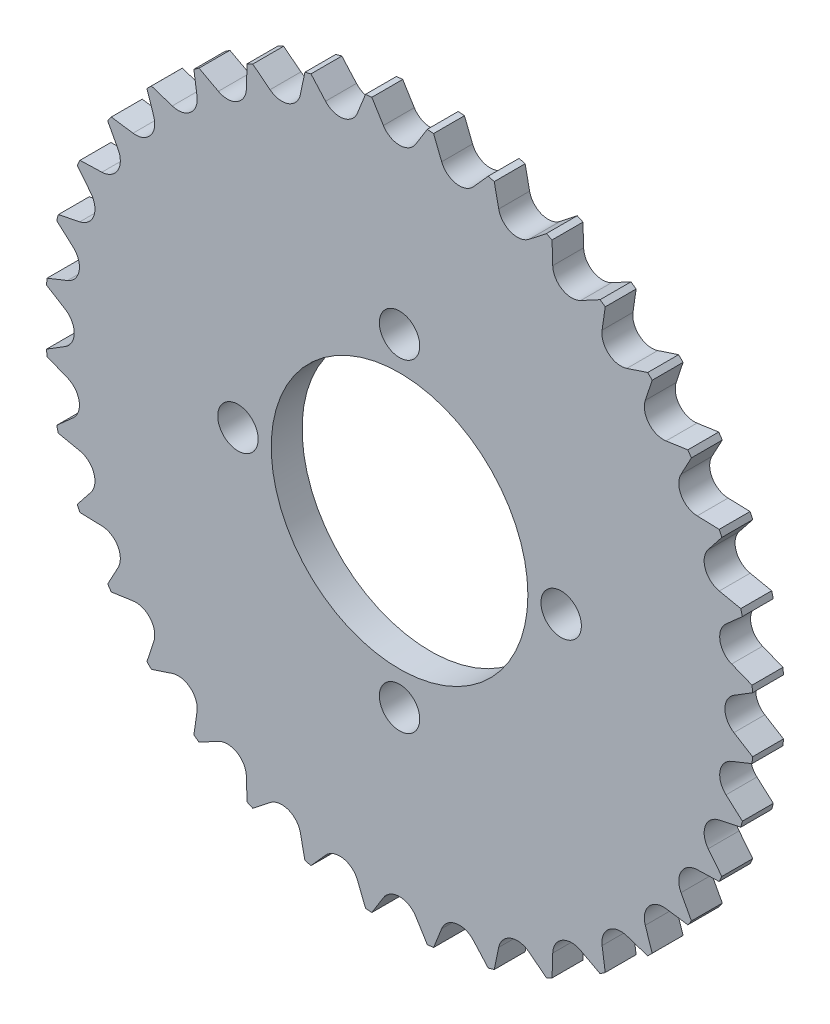
SolidWorks part; units mm, degrees
material "Plain Carbon Steel"
ref_plane "Front Plane" through (0, 0, 0) normal (0, 0, 1) x (1, 0, 0)
ref_plane "Top Plane" through (0, 0, 0) normal (0, 1, 0) x (1, 0, 0)
ref_plane "Right Plane" through (0, 0, 0) normal (1, 0, 0) x (0, 0, -1)
sketch "Sketch1" plane through (0, 0, 0) normal (0, 0, 1) x (1, 0, 0)
  line L0 (3.4006, 70.3439) -> (6.0855, 74.679)
  line L1 (3.4006, 70.3439) -> (8.8661, 69.8657) construction
  line L2 (6.9749, 74.6012) -> (8.8661, 69.8657)
  line L3 (3.4006, 70.3439) -> (0, 0) construction
  line L4 (0, 0) -> (8.8661, 69.8657) construction
  line L5 (15.5641, 68.6847) -> (18.9609, 72.4877)
  line L6 (19.8233, 72.2567) -> (20.8635, 67.2647)
  line L7 (27.2546, 64.9386) -> (31.2602, 68.094)
  line L8 (32.0693, 67.7166) -> (32.2269, 62.6199)
  line L9 (38.117, 59.2193) -> (42.6097, 61.6312)
  line L10 (43.341, 61.1191) -> (42.6111, 56.0725)
  line L11 (47.8212, 51.7007) -> (52.6645, 53.2958)
  line L12 (53.2958, 52.6645) -> (51.7007, 47.8212)
  line L13 (56.0725, 42.6111) -> (61.1191, 43.341)
  line L14 (61.6312, 42.6097) -> (59.2193, 38.117)
  line L15 (62.6199, 32.2269) -> (67.7166, 32.0693)
  line L16 (68.094, 31.2602) -> (64.9386, 27.2546)
  line L17 (67.2647, 20.8635) -> (72.2567, 19.8233)
  line L18 (72.4877, 18.9609) -> (68.6847, 15.5641)
  line L19 (69.8657, 8.8661) -> (74.6012, 6.9749)
  line L20 (74.679, 6.0855) -> (70.3439, 3.4006)
  line L21 (70.3439, -3.4006) -> (74.679, -6.0855)
  line L22 (74.6012, -6.9749) -> (69.8657, -8.8661)
  line L23 (68.6847, -15.5641) -> (72.4877, -18.9609)
  line L24 (72.2567, -19.8233) -> (67.2647, -20.8635)
  line L25 (64.9386, -27.2546) -> (68.094, -31.2602)
  line L26 (67.7166, -32.0693) -> (62.6199, -32.2269)
  line L27 (59.2193, -38.117) -> (61.6312, -42.6097)
  line L28 (61.1191, -43.341) -> (56.0725, -42.6111)
  line L29 (51.7007, -47.8212) -> (53.2958, -52.6645)
  line L30 (52.6645, -53.2958) -> (47.8212, -51.7007)
  line L31 (42.6111, -56.0725) -> (43.341, -61.1191)
  line L32 (42.6097, -61.6312) -> (38.117, -59.2193)
  line L33 (32.2269, -62.6199) -> (32.0693, -67.7166)
  line L34 (31.2602, -68.094) -> (27.2546, -64.9386)
  line L35 (20.8635, -67.2647) -> (19.8233, -72.2567)
  line L36 (18.9609, -72.4877) -> (15.5641, -68.6847)
  line L37 (8.8661, -69.8657) -> (6.9749, -74.6012)
  line L38 (6.0855, -74.679) -> (3.4006, -70.3439)
  line L39 (-3.4006, -70.3439) -> (-6.0855, -74.679)
  line L40 (-6.9749, -74.6012) -> (-8.8661, -69.8657)
  line L41 (-15.5641, -68.6847) -> (-18.9609, -72.4877)
  line L42 (-19.8233, -72.2567) -> (-20.8635, -67.2647)
  line L43 (-27.2546, -64.9386) -> (-31.2602, -68.094)
  line L44 (-32.0693, -67.7166) -> (-32.2269, -62.6199)
  line L45 (-38.117, -59.2193) -> (-42.6097, -61.6312)
  line L46 (-43.341, -61.1191) -> (-42.6111, -56.0725)
  line L47 (-47.8212, -51.7007) -> (-52.6645, -53.2958)
  line L48 (-53.2958, -52.6645) -> (-51.7007, -47.8212)
  line L49 (-56.0725, -42.6111) -> (-61.1191, -43.341)
  line L50 (-61.6312, -42.6097) -> (-59.2193, -38.117)
  line L51 (-62.6199, -32.2269) -> (-67.7166, -32.0693)
  line L52 (-68.094, -31.2602) -> (-64.9386, -27.2546)
  line L53 (-67.2647, -20.8635) -> (-72.2567, -19.8233)
  line L54 (-72.4877, -18.9609) -> (-68.6847, -15.5641)
  line L55 (-69.8657, -8.8661) -> (-74.6012, -6.9749)
  line L56 (-74.679, -6.0855) -> (-70.3439, -3.4006)
  line L57 (-70.3439, 3.4006) -> (-74.679, 6.0855)
  line L58 (-74.6012, 6.9749) -> (-69.8657, 8.8661)
  line L59 (-68.6847, 15.5641) -> (-72.4877, 18.9609)
  line L60 (-72.2567, 19.8233) -> (-67.2647, 20.8635)
  line L61 (-64.9386, 27.2546) -> (-68.094, 31.2602)
  line L62 (-67.7166, 32.0693) -> (-62.6199, 32.2269)
  line L63 (-59.2193, 38.117) -> (-61.6312, 42.6097)
  line L64 (-61.1191, 43.341) -> (-56.0725, 42.6111)
  line L65 (-51.7007, 47.8212) -> (-53.2958, 52.6645)
  line L66 (-52.6645, 53.2958) -> (-47.8212, 51.7007)
  line L67 (-42.6111, 56.0725) -> (-43.341, 61.1191)
  line L68 (-42.6097, 61.6312) -> (-38.117, 59.2193)
  line L69 (-32.2269, 62.6199) -> (-32.0693, 67.7166)
  line L70 (-31.2602, 68.094) -> (-27.2546, 64.9386)
  line L71 (-20.8635, 67.2647) -> (-19.8233, 72.2567)
  line L72 (-18.9609, 72.4877) -> (-15.5641, 68.6847)
  line L73 (-8.8661, 69.8657) -> (-6.9749, 74.6012)
  line L74 (-6.0855, 74.679) -> (-3.4006, 70.3439)
  line L83 (0, 72.45) -> (0, 0) construction
  line L84 (0, 0) -> (6.5105, 74.4157) construction
  circle A0 centre (0, 0) radius 72.45 construction
  arc A1 (-3.9985, 72.3396) -> (3.4006, 70.3439) centre (0, 72.45) ccw
  arc A2 (4.6139, 72.3029) -> (8.0115, 72.0057) centre (0, 0) cw
  arc A3 (6.0855, 74.679) -> (6.9749, 74.6012) centre (6.5105, 74.4157) cw
  arc A4 (8.6239, 71.9349) -> (15.5641, 68.6847) centre (12.5808, 71.3493) ccw
  arc A5 (18.9609, 72.4877) -> (19.8233, 72.2567) centre (19.3338, 72.1547) cw
  arc A6 (20.9843, 69.3445) -> (27.2546, 64.9386) centre (24.7794, 68.0807) ccw
  arc A7 (31.2602, 68.094) -> (32.0693, 67.7166) centre (31.5696, 67.7012) cw
  arc A8 (32.707, 64.6472) -> (38.117, 59.2193) centre (36.225, 62.7435) ccw
  arc A9 (42.6097, 61.6312) -> (43.341, 61.1191) centre (42.8462, 61.1907) cw
  arc A10 (43.436, 57.9855) -> (47.8212, 51.7007) centre (46.57, 55.4999) ccw
  arc A11 (52.6645, 53.2958) -> (53.2958, 52.6645) centre (52.8209, 52.8209) cw
  arc A12 (52.8452, 49.562) -> (56.0725, 42.6111) centre (55.4999, 46.57) ccw
  arc A13 (61.1191, 43.341) -> (61.6312, 42.6097) centre (61.1907, 42.8462) cw
  arc A14 (60.6487, 39.6326) -> (62.6199, 32.2269) centre (62.7435, 36.225) ccw
  arc A15 (67.7166, 32.0693) -> (68.094, 31.2602) centre (67.7012, 31.5696) cw
  arc A16 (66.6094, 28.4989) -> (67.2647, 20.8635) centre (68.0807, 24.7794) ccw
  arc A17 (72.2567, 19.8233) -> (72.4877, 18.9609) centre (72.1547, 19.3338) cw
  arc A18 (70.5463, 16.4994) -> (69.8657, 8.8661) centre (71.3493, 12.5808) ccw
  arc A19 (74.6012, 6.9749) -> (74.679, 6.0855) centre (74.4157, 6.5105) cw
  arc A20 (72.3396, 3.9985) -> (70.3439, -3.4006) centre (72.45, 0) ccw
  arc A21 (74.679, -6.0855) -> (74.6012, -6.9749) centre (74.4157, -6.5105) cw
  arc A22 (71.9349, -8.6239) -> (68.6847, -15.5641) centre (71.3493, -12.5808) ccw
  arc A23 (72.4877, -18.9609) -> (72.2567, -19.8233) centre (72.1547, -19.3338) cw
  arc A24 (69.3445, -20.9843) -> (64.9386, -27.2546) centre (68.0807, -24.7794) ccw
  arc A25 (68.094, -31.2602) -> (67.7166, -32.0693) centre (67.7012, -31.5696) cw
  arc A26 (64.6472, -32.707) -> (59.2193, -38.117) centre (62.7435, -36.225) ccw
  arc A27 (61.6312, -42.6097) -> (61.1191, -43.341) centre (61.1907, -42.8462) cw
  arc A28 (57.9855, -43.436) -> (51.7007, -47.8212) centre (55.4999, -46.57) ccw
  arc A29 (53.2958, -52.6645) -> (52.6645, -53.2958) centre (52.8209, -52.8209) cw
  arc A30 (49.562, -52.8452) -> (42.6111, -56.0725) centre (46.57, -55.4999) ccw
  arc A31 (43.341, -61.1191) -> (42.6097, -61.6312) centre (42.8462, -61.1907) cw
  arc A32 (39.6326, -60.6487) -> (32.2269, -62.6199) centre (36.225, -62.7435) ccw
  arc A33 (32.0693, -67.7166) -> (31.2602, -68.094) centre (31.5696, -67.7012) cw
  arc A34 (28.4989, -66.6094) -> (20.8635, -67.2647) centre (24.7794, -68.0807) ccw
  arc A35 (19.8233, -72.2567) -> (18.9609, -72.4877) centre (19.3338, -72.1547) cw
  arc A36 (16.4994, -70.5463) -> (8.8661, -69.8657) centre (12.5808, -71.3493) ccw
  arc A37 (6.9749, -74.6012) -> (6.0855, -74.679) centre (6.5105, -74.4157) cw
  arc A38 (3.9985, -72.3396) -> (-3.4006, -70.3439) centre (0, -72.45) ccw
  arc A39 (-6.0855, -74.679) -> (-6.9749, -74.6012) centre (-6.5105, -74.4157) cw
  arc A40 (-8.6239, -71.9349) -> (-15.5641, -68.6847) centre (-12.5808, -71.3493) ccw
  arc A41 (-18.9609, -72.4877) -> (-19.8233, -72.2567) centre (-19.3338, -72.1547) cw
  arc A42 (-20.9843, -69.3445) -> (-27.2546, -64.9386) centre (-24.7794, -68.0807) ccw
  arc A43 (-31.2602, -68.094) -> (-32.0693, -67.7166) centre (-31.5696, -67.7012) cw
  arc A44 (-32.707, -64.6472) -> (-38.117, -59.2193) centre (-36.225, -62.7435) ccw
  arc A45 (-42.6097, -61.6312) -> (-43.341, -61.1191) centre (-42.8462, -61.1907) cw
  arc A46 (-43.436, -57.9855) -> (-47.8212, -51.7007) centre (-46.57, -55.4999) ccw
  arc A47 (-52.6645, -53.2958) -> (-53.2958, -52.6645) centre (-52.8209, -52.8209) cw
  arc A48 (-52.8452, -49.562) -> (-56.0725, -42.6111) centre (-55.4999, -46.57) ccw
  arc A49 (-61.1191, -43.341) -> (-61.6312, -42.6097) centre (-61.1907, -42.8462) cw
  arc A50 (-60.6487, -39.6326) -> (-62.6199, -32.2269) centre (-62.7435, -36.225) ccw
  arc A51 (-67.7166, -32.0693) -> (-68.094, -31.2602) centre (-67.7012, -31.5696) cw
  arc A52 (-66.6094, -28.4989) -> (-67.2647, -20.8635) centre (-68.0807, -24.7794) ccw
  arc A53 (-72.2567, -19.8233) -> (-72.4877, -18.9609) centre (-72.1547, -19.3338) cw
  arc A54 (-70.5463, -16.4994) -> (-69.8657, -8.8661) centre (-71.3493, -12.5808) ccw
  arc A55 (-74.6012, -6.9749) -> (-74.679, -6.0855) centre (-74.4157, -6.5105) cw
  arc A56 (-72.3396, -3.9985) -> (-70.3439, 3.4006) centre (-72.45, 0) ccw
  arc A57 (-74.679, 6.0855) -> (-74.6012, 6.9749) centre (-74.4157, 6.5105) cw
  arc A58 (-71.9349, 8.6239) -> (-68.6847, 15.5641) centre (-71.3493, 12.5808) ccw
  arc A59 (-72.4877, 18.9609) -> (-72.2567, 19.8233) centre (-72.1547, 19.3338) cw
  arc A60 (-69.3445, 20.9843) -> (-64.9386, 27.2546) centre (-68.0807, 24.7794) ccw
  arc A61 (-68.094, 31.2602) -> (-67.7166, 32.0693) centre (-67.7012, 31.5696) cw
  arc A62 (-64.6472, 32.707) -> (-59.2193, 38.117) centre (-62.7435, 36.225) ccw
  arc A63 (-61.6312, 42.6097) -> (-61.1191, 43.341) centre (-61.1907, 42.8462) cw
  arc A64 (-57.9855, 43.436) -> (-51.7007, 47.8212) centre (-55.4999, 46.57) ccw
  arc A65 (-53.2958, 52.6645) -> (-52.6645, 53.2958) centre (-52.8209, 52.8209) cw
  arc A66 (-49.562, 52.8452) -> (-42.6111, 56.0725) centre (-46.57, 55.4999) ccw
  arc A67 (-43.341, 61.1191) -> (-42.6097, 61.6312) centre (-42.8462, 61.1907) cw
  arc A68 (-39.6326, 60.6487) -> (-32.2269, 62.6199) centre (-36.225, 62.7435) ccw
  arc A69 (-32.0693, 67.7166) -> (-31.2602, 68.094) centre (-31.5696, 67.7012) cw
  arc A70 (-28.4989, 66.6094) -> (-20.8635, 67.2647) centre (-24.7794, 68.0807) ccw
  arc A71 (-19.8233, 72.2567) -> (-18.9609, 72.4877) centre (-19.3338, 72.1547) cw
  arc A72 (-16.4994, 70.5463) -> (-8.8661, 69.8657) centre (-12.5808, 71.3493) ccw
  arc A73 (-6.9749, 74.6012) -> (-6.0855, 74.679) centre (-6.5105, 74.4157) cw
  point P289 (0, 0)
  dimension "D1" = 144.9
  dimension "D2" = 4
  dimension "D5" = 0.5
  dimension "D6" = 74.7
  dimension "D3" = 5
  dimension "D4" = 36
extrude "Boss-Extrude1" add sketch "Sketch1" along normal blind 6.5 contours L74 A73 L73 A72 L72 A71 L71 A70 L70 A69 L69 A68 L68 A67 L67 A66 L66 A65 L65 A64 L64 A63 L63 A62 L62 A61 L61 A60 L60 A59 L59 A58 L58 A57 L57 A56 | A3 L0 A2 L2 region at (-0.0022, -0.0255, 0) region at (6.4054, 73.214, 0)
sketch "Sketch5" plane through (0, 0, 0) normal (0, 0, -1) x (-1, 0, 0)
  line L0 (0, 68.45) -> (2.9886, 68.1885)
  line L1 (0, 68.45) -> (0.611, 75.4338)
  line L2 (11.8862, 67.4101) -> (12.4972, 74.3939)
  line L3 (0.611, 75.4338) -> (12.4972, 74.3939)
  line L4 (8.8976, 67.6716) -> (11.8862, 67.4101)
  arc A0 (2.9886, 68.1885) -> (8.8976, 67.6716) centre (6.3977, 73.1259) ccw
  arc A3 (-3.4006, 70.3439) -> (3.4006, 70.3439) centre (0, 72.45) ccw construction
  arc A5 (-3.4006, 70.3439) -> (3.4006, 70.3439) centre (0, 72.45) ccw construction
  arc A7 (8.8661, 69.8657) -> (15.5641, 68.6847) centre (12.5808, 71.3493) ccw construction
  arc A8 (6.9749, 74.6012) -> (6.0855, 74.679) centre (6.5105, 74.4157) ccw construction
  point P19 (0, 68.45)
  point P22 (11.8862, 67.4101)
  dimension "D2" = 3
  dimension "D3" = 3
  dimension "D4" = 6
extrude "Cut-Extrude2" [suppressed] cut sketch "Sketch5" against normal blind 10
sketch "Sketch9" plane through (0, 0, 0) normal (0, 0, -1) x (-1, 0, 0)
  circle A0 centre (0, 0) radius 74.5
  circle A1 centre (0, 0) radius 100
  dimension "D1" = 149
  dimension "D2" = 200
extrude "Cut-Extrude5" cut sketch "Sketch9" against normal blind 10
sketch "Sketch10" plane through (0, 0, 6.5) normal (0, 0, 1) x (1, 0, 0)
  circle A0 centre (0, 0) radius 27
  circle A1 centre (0, 34) radius 4.25
  circle A2 centre (34, 0) radius 4.25
  circle A3 centre (0, -34) radius 4.25
  circle A4 centre (-34, 0) radius 4.25
  point P14 (0, 0)
  dimension "D1" = 54
  dimension "D2" = 8.5
  dimension "D3" = 34
  dimension "D4" = 4
extrude "Cut-Extrude6" cut sketch "Sketch10" against normal through all
equation "\"Teeth\"= 36"
equation "\"D4@Sketch1\"=\"Teeth\""
equation "\"D6@Sketch1\"=83/40*\"Teeth\""
equation "\"D1@Sketch1\"=161/40*\"Teeth\""
equation "\"D3@Sketch1\"=4.5/\"Teeth\"*40"
